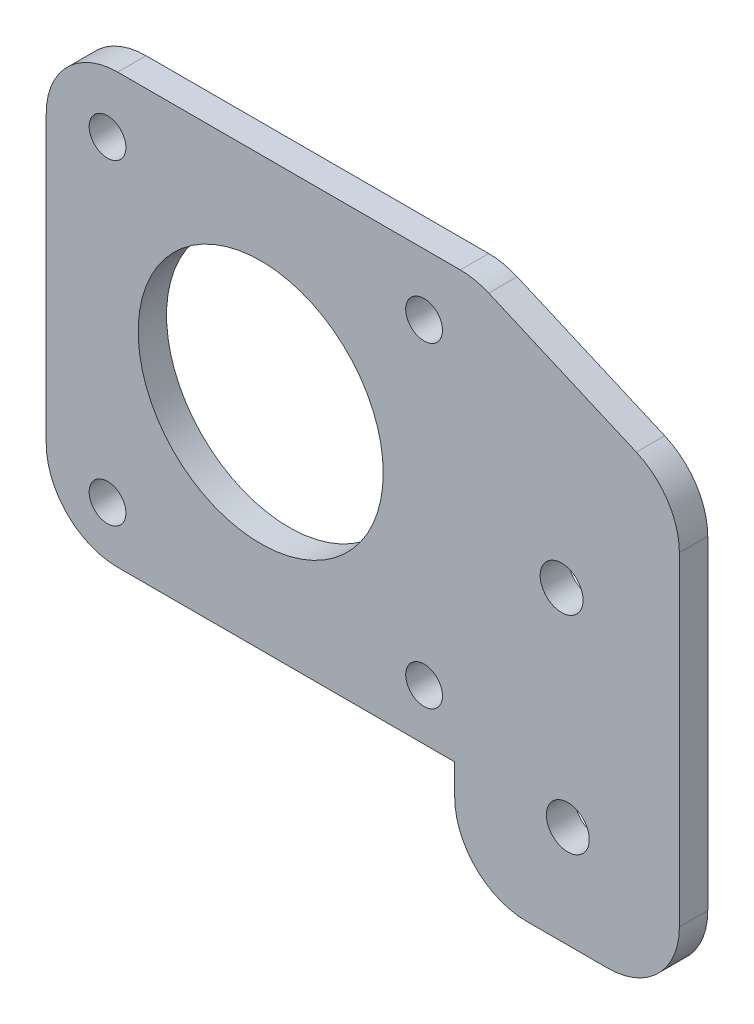
SolidWorks part; units mm, degrees
ref_plane "Front Plane" through (0, 0, 0) normal (0, 0, 1) x (1, 0, 0)
ref_plane "Top Plane" through (0, 0, 0) normal (0, 1, 0) x (1, 0, 0)
ref_plane "Right Plane" through (0, 0, 0) normal (1, 0, 0) x (0, 0, -1)
sketch "Sketch1" plane through (0, 0, 0) normal (0, 0, 1) x (1, 0, 0)
  line L1 (-62, 30.4655) -> (0, 30.4655)
  line L2 (-62, 30.4655) -> (-62, -21.5345)
  line L3 (-62, -21.5345) -> (0, -21.5345)
  line L4 (0, 30.4655) -> (0, -21.5345)
  dimension "D1" = 62
  dimension "D2" = 52
extrude "Boss-Extrude1" add sketch "Sketch1" along normal blind 2.7781
sketch "Sketch2" plane through (0, 0, 2.7781) normal (0, 0, 1) x (1, 0, 0)
  line L1 (-62, -21.5345) -> (-22, -21.5345)
  line L2 (-62, -21.5345) -> (-62, -11.5345)
  line L3 (-62, -11.5345) -> (-22, -11.5345)
  line L4 (-22, -21.5345) -> (-22, -11.5345)
  dimension "D1" = 40
  dimension "D2" = 10
sketch "Sketch3" plane through (0, 0, 2.7781) normal (0, 0, 1) x (1, 0, 0)
  line L0 (-20, 30.4655) -> (0, 21.8025)
  line L7 (-20, 30.4655) -> (0, 30.4655)
  line L8 (0, 30.4655) -> (0, 21.8025)
extrude "Cut-Extrude1" cut sketch "Sketch3" against normal blind 10
extrude "Cut-Extrude2" cut sketch "Sketch2" against normal blind 10
fillet "Fillet1" radius 7 4 edges at (0, -21.5345, 1.3891) (-22, -21.5345, 1.3891) (-62, -11.5345, 1.3891) (-62, 30.4655, 1.3891)
fillet "Fillet2" radius 7 2 edges at (-20, 30.4655, 1.3891) (0, 21.8025, 1.3891)
sketch "Sketch4" plane through (0, 0, 2.7781) normal (0, 0, 1) x (1, 0, 0)
  line L0 (-15, -21.5345) -> (-7, -21.5345) construction
  line L1 (-62, 23.4655) -> (-62, -4.5345) construction
  line L2 (-21.4509, 30.4655) -> (-55, 30.4655) construction
  circle A0 centre (-10.926, -11.5345) radius 2.1
  circle A1 centre (-11.5335, 8.4655) radius 2.1
  circle A2 centre (-56, -6.5345) radius 1.8
  circle A3 centre (-56, 24.4655) radius 1.8
  circle A4 centre (-25, 24.4655) radius 1.8
  circle A5 centre (-25, -6.5345) radius 1.8
  circle A6 centre (-41, 9.4682) radius 12
  point P20 (0, 0)
  point P21 (-42.5565, 12.4592)
  point P22 (-42.4587, 9.4682)
  dimension "D1" = 20
  dimension "D3" = 31
  dimension "D5" = 6
  dimension "D10" = 21
  dimension "D2" = 10
  dimension "D4" = 31
  dimension "D6" = 6
  dimension "D7" = 31
  dimension "D8" = 6
  dimension "D9" = 6
extrude "Cut-Extrude3" cut sketch "Sketch4" against normal blind 10
